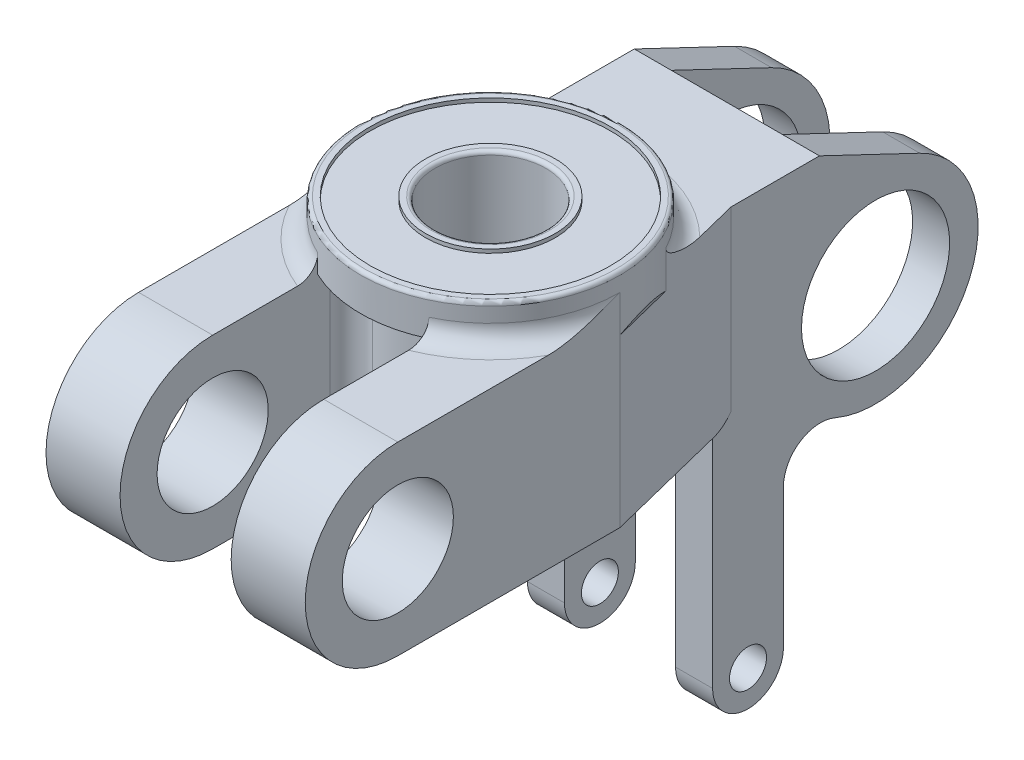
SolidWorks part; units mm, degrees
note: The reader was unsure of these and kept them because the rebuilt part matched: shared geometry of "Sketch6<4>".
material "1060 Alloy"
ref_plane "Front Plane" through (0, 0, 0) normal (0, 0, 1) x (1, 0, 0)
ref_plane "Top Plane" through (0, 0, 0) normal (0, 1, 0) x (1, 0, 0)
ref_plane "Right Plane" through (0, 0, 0) normal (1, 0, 0) x (0, 0, -1)
sketch "Sketch1" plane through (0, 0, 0) normal (0, 1, 0) x (1, 0, 0)
  line L15 (-12.5, 30) -> (12.5, 30)
  line L16 (12.5, 30) -> (12.5, 10)
  line L17 (12.5, 10) -> (17.5, -10)
  line L18 (17.5, -10) -> (17.5, -60)
  line L19 (17.5, -60) -> (7.5, -60)
  line L20 (7.5, -60) -> (7.5, -20)
  line L23 (0, -55) -> (0, 55) construction
  line L25 (-7.5, -60) -> (-7.5, -20)
  line L26 (-17.5, -60) -> (-7.5, -60)
  line L27 (-17.5, -10) -> (-17.5, -60)
  line L28 (-12.5, 10) -> (-17.5, -10)
  line L29 (-12.5, 30) -> (-12.5, 10)
  arc A0 (-7.5, -10) -> (7.5, -10) centre (0, -10) cw
  arc A1 (-7.5, -10) -> (7.5, -10) centre (0, -10) ccw
  arc A2 (-7.5, -20) -> (7.5, -20) centre (0, -10) ccw
  arc A4 (-12.5, -10) -> (12.5, -10) centre (0, -10) ccw construction
  point P14 (0, 0)
  point P20 (0, 30)
  dimension "D1" = 12.5
  dimension "D2" = 10
  dimension "D3" = 7.5
  dimension "D4" = 60
  dimension "D5" = 10
  dimension "D7" = 30
  dimension "D8" = 5
  dimension "D9" = 10
extrude "Boss-Extrude1" add sketch "Sketch1" along normal blind 30
sketch "Sketch2" plane through (0, 0, 0) normal (1, 0, 0) x (0, 0, -1)
  line L0 (-40, 30) -> (10, 30)
  line L6 (10, 30) -> (10, 0) construction
  line L7 (10, 5) -> (-40, 5)
  line L10 (-60, 30) -> (-10, 30) construction
  line L14 (10, 5) -> (21.9244, 30)
  line L15 (21.9244, 30) -> (10, 30)
  circle A0 centre (-40, 17.5) radius 7.5
  arc A1 (-40, 30) -> (-40, 5) centre (-40, 17.5) ccw
  dimension "D4" = 15
  dimension "D1" = 25
  dimension "D2" = 50
  dimension "D3" = 25.5
extrude "Cut-Extrude1" cut sketch "Sketch2" along normal through all both and the other way through all flip side to cut
sketch "Sketch4" plane through (0, 30, 0) normal (0, 1, 0) x (1, 0, 0)
  circle A0 centre (0, -10) radius 17.5
  circle A1 centre (0, -10) radius 7.5
  circle A2 centre (0, -10) radius 7.5 construction
  dimension "D1" = 35
fillet "Fillet1" radius 2.5 2 edges at (-7.5, 17.5, 20) (7.5, 17.5, 20)
extrude "Boss-Extrude2" add sketch "Sketch4" along normal blind 5
fillet "Fillet3" radius 2.5 3 edges at (14.7902, 30, 19.3541) (0, 30, -7.5) (-14.7902, 30, 19.3541)
sketch "Sketch5" plane through (0, 35, 0) normal (0, 1, 0) x (1, 0, 0)
  circle A0 centre (0, -10) radius 16.25
  circle A1 centre (0, -10) radius 17.5 construction
  circle A2 centre (0, -10) radius 8.75
  circle A3 centre (0, -10) radius 7.5 construction
  dimension "D1" = 1.25
  dimension "D2" = 1.25
extrude "Cut-Extrude2" cut sketch "Sketch5" against normal blind 0.5
fillet "Fillet13" radius 0.5 2 edges at (0, 35, 27.5) (0, 35, 17.5)
chamfer "Chamfer1" distance 2.5 angle 25 2 edges at (-16.4706, 30, 5.8824) (16.4706, 30, 5.8824)
sketch "Sketch6" plane through (0, 0, 0) normal (1, 0, 0) x (0, 0, -1)
  line L0 (21.9244, 30) -> (35.4632, 23.5423)
  line L1 (10, 5) -> (23.5388, -1.4577)
  line L2 (10, 5) -> (21.9244, 30) construction
  line L3 (21.9244, 30) -> (10, 5)
  line L5 (7.5, 5) -> (7.5, -25.0611)
  line L6 (-10, 5) -> (10, 5) construction
  line L7 (29.501, 11.0423) -> (12.2805, -25.0611) construction
  line L8 (17.0611, -25.0611) -> (17.0611, 1.632)
  line L9 (17.0611, 1.632) -> (10, 5)
  line L10 (7.5, 5) -> (10, 5)
  arc A0 (35.4632, 23.5423) -> (23.5388, -1.4577) centre (29.501, 11.0423) cw
  circle A1 centre (29.501, 11.0423) radius 10
  arc A2 (7.5, -25.0611) -> (17.0611, -25.0611) centre (12.2805, -25.0611) ccw
  circle A3 centre (12.2805, -25.0611) radius 2.5
  point P16 (15.6412, 2.3093)
  point P19 (0, 0)
  dimension "D2" = 20
  dimension "D4" = 5
  dimension "D1" = 15
  dimension "D3" = 40
  dimension "D5" = 2.5
extrude "Boss-Extrude4" add sketch "Sketch6" along normal up to vertex and the other way up to vertex
extrude "Cut-Extrude4" cut sketch "Sketch6<4>" against normal mid plane 15
sketch "Sketch6<4>" plane through (0, 0, 0) normal (1, 0, 0) x (0, 0, -1) same geometry as "Sketch6"
fillet "Fillet14" radius 5 3 edges at (10, 1.632, -17.0611) (-10, 1.632, -17.0611) (0, 5, -10)
